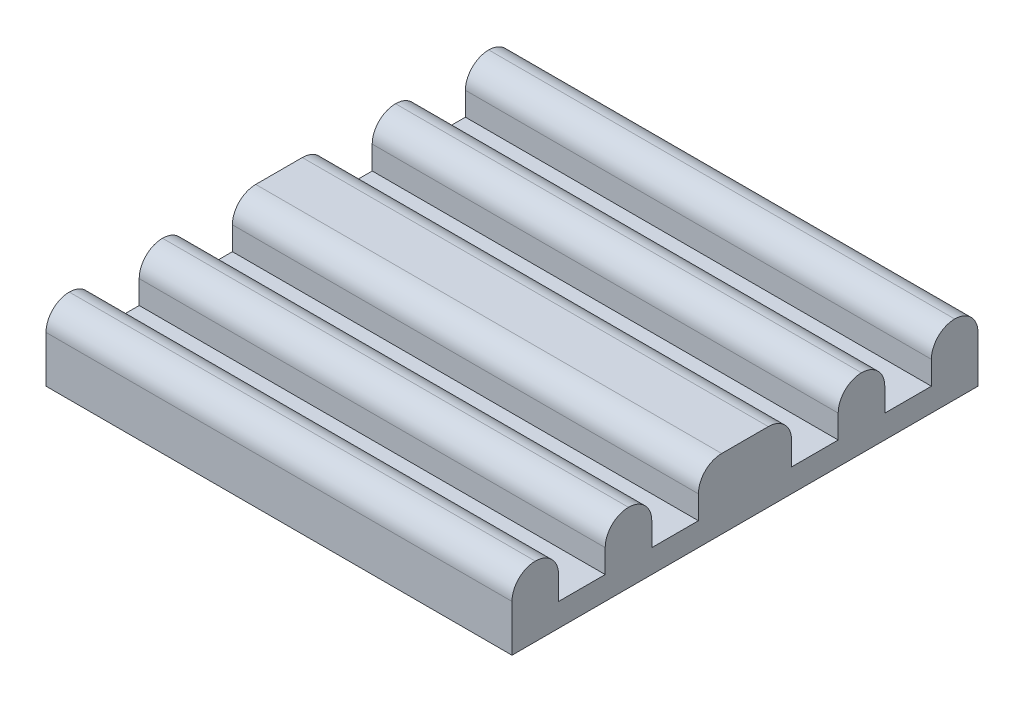
SolidWorks part; units mm, degrees
ref_plane "前视基准面" through (0, 0, 0) normal (0, 0, 1) x (1, 0, 0)
ref_plane "上视基准面" through (0, 0, 0) normal (0, 1, 0) x (1, 0, 0)
ref_plane "右视基准面" through (0, 0, 0) normal (1, 0, 0) x (0, 0, -1)
other "Configuration Table"
sketch "草图1" plane through (0, 0, 0) normal (0, 1, 0) x (1, 0, 0)
  line L1 (-10, 10) -> (10, 10)
  line L2 (-10, 10) -> (-10, -10)
  line L3 (-10, -10) -> (10, -10)
  line L4 (10, 10) -> (10, -10)
  line L5 (-10, 10) -> (10, -10) construction
  line L6 (-10, -10) -> (10, 10) construction
  point P0 (0, 0)
  dimension "D1" = 20
  dimension "D2" = 20
extrude "凸台-拉伸1" add sketch "草图1" along normal blind 3
sketch "草图2" plane through (0, 3, 0) normal (0, 1, 0) x (1, 0, 0)
  line L0 (-10, -8) -> (10, -8)
  line L1 (-15.0285, 12.7873) -> (-15.0285, -7.7824) construction
  line L2 (-10, -6) -> (10, -6)
  line L3 (-10, -4) -> (10, -4)
  line L4 (10, 10) -> (-10, 10)
  line L5 (10, -10) -> (10, 10)
  line L6 (-10, -10) -> (10, -10)
  line L7 (-10, 10) -> (-10, -10)
  line L8 (10, 10) -> (-10, 10)
  line L9 (10, -10) -> (10, 10)
  line L10 (-10, -10) -> (10, -10)
  line L11 (-10, 10) -> (-10, -10)
  line L12 (-10, -2) -> (10, -2)
  line L13 (-10, 0) -> (10, 0)
  line L14 (-10, 2) -> (10, 2)
  line L15 (-10, 4) -> (10, 4)
  line L16 (-10, 6) -> (10, 6)
  line L17 (-10, 8) -> (10, 8)
  line L18 (-10, 10) -> (10, 10)
  line M7 (10, -10) -> (10, 10)
  line M9 (-10, 10) -> (-10, -10)
  dimension "D2" = 2
  dimension "D3" = 10
  dimension "D1" = 0
extrude "切除-拉伸1" cut sketch "草图2" against normal blind 2 contours L2 L0 M9 M7 | L12 L11 L3 M7 | L17 L11 L16 L9 | L15 L11 L14 L9 region at (0, 3, 7) region at (0, 3, 3) region at (0, 3, -3) region at (0, 3, -7)
fillet "圆角1" radius 1 10 edges at (0, 3, 10) (0, 3, 8) (0, 3, 6) (0, 3, 4) (0, 3, 2) (0, 3, -2) (0, 3, -4) (0, 3, -6) (0, 3, -8) (0, 3, -10)
